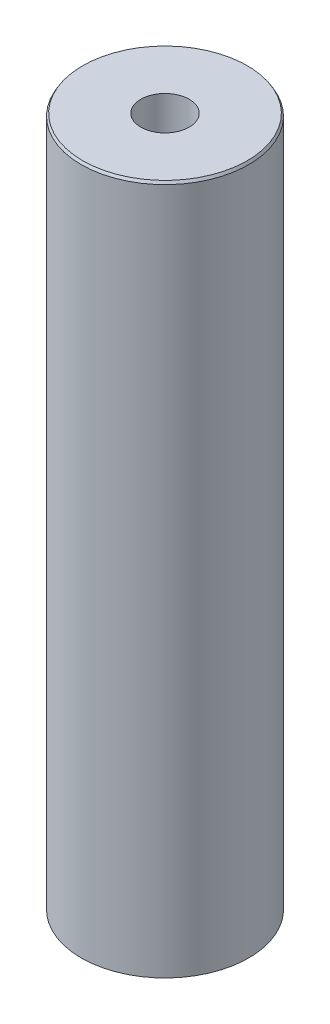
SolidWorks part; units mm, degrees
ref_plane "Front Plane" through (0, 0, 0) normal (0, 0, 1) x (1, 0, 0)
ref_plane "Top Plane" through (0, 0, 0) normal (0, 1, 0) x (1, 0, 0)
ref_plane "Right Plane" through (0, 0, 0) normal (1, 0, 0) x (0, 0, -1)
sketch "Sketch1" plane through (0, 0, 0) normal (0, 1, 0) x (1, 0, 0)
  circle A0 centre (0, 0) radius 30
  dimension "SHAFT_OD" = 60
extrude "Boss-Extrude1" add sketch "Sketch1" along normal blind 247.3764
sketch "Sketch2" plane through (0, 0, 0) normal (0, 1, 0) x (1, 0, 0)
  circle A0 centre (0, 0) radius 8.6651
  dimension "BORE_D" = 17.3302
extrude "Cut-Extrude1" cut sketch "Sketch2" along normal through all
chamfer "Chamfer1" distance 0.9352 angle 30 2 edges at (0, 247.3764, 30) (0, 0, 30) first distance on face at (0, 247.3764, 30) first distance on face at (0, 0, 8.6651)
